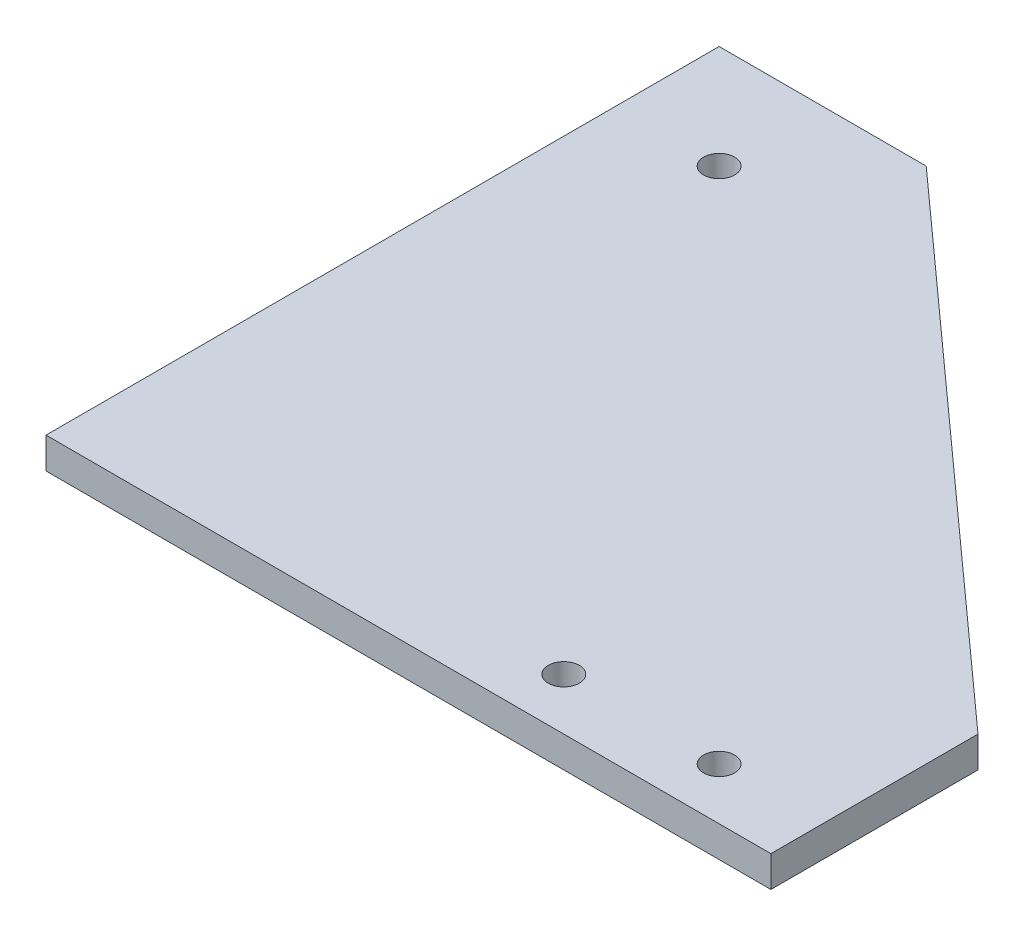
SolidWorks part; units mm, degrees
ref_plane "Plan de face" through (0, 0, 0) normal (0, 0, 1) x (1, 0, 0)
ref_plane "Plan de dessus" through (0, 0, 0) normal (0, 1, 0) x (1, 0, 0)
ref_plane "Plan de droite" through (0, 0, 0) normal (1, 0, 0) x (0, 0, -1)
sketch "Sketch1" plane through (0, 0, 0) normal (0, 1, 0) x (1, 0, 0)
  line L1 (35.5792, -33.0378) -> (-34.4208, -33.0378)
  line L2 (35.5792, -33.0378) -> (35.5792, -13.0378)
  line L3 (-14.4208, 31.9622) -> (-34.4208, 31.9622)
  line L4 (-34.4208, -33.0378) -> (-34.4208, 31.9622)
  line L5 (35.5792, -33.0378) -> (-34.4208, 31.9622) construction
  line L6 (10.2071, 9.797) -> (-34.4208, -33.0378) construction
  line L7 (-14.4208, 31.9622) -> (35.5792, -13.0378)
  circle A1 centre (25.5792, -28.0378) radius 1.5
  point P0 (0, 0)
  dimension "D4" = 10
  dimension "D6" = 3
  dimension "D1" = 70
  dimension "D2" = 65
  dimension "D3" = 20
  dimension "D5" = 20
  dimension "D7" = 5
extrude "Boss-Extrude1" add sketch "Sketch1" along normal blind 3
sketch "Sketch4" plane through (0, 3, 0) normal (0, 1, 0) x (-1, 0, 0)
  line L0 (-35.5792, 33.0378) -> (-35.5792, 13.0378) construction
  line L1 (34.4208, 33.0378) -> (-35.5792, 33.0378) construction
  circle A0 centre (-10.5792, 28.0378) radius 1.5
  dimension "D1" = 25
  dimension "D3" = 3
  dimension "D2" = 5
extrude "Cut-Extrude1" cut sketch "Sketch4" against normal blind 5
sketch "Sketch5" plane through (0, 3, 0) normal (0, 1, 0) x (-1, 0, 0)
  line L0 (34.4208, -31.9622) -> (34.4208, 33.0378) construction
  line L1 (14.4208, -31.9622) -> (34.4208, -31.9622) construction
  circle A0 centre (24.4208, -21.9622) radius 1.5
  dimension "D1" = 10
  dimension "D3" = 3
  dimension "D2" = 10
extrude "Cut-Extrude2" cut sketch "Sketch5" against normal through all
